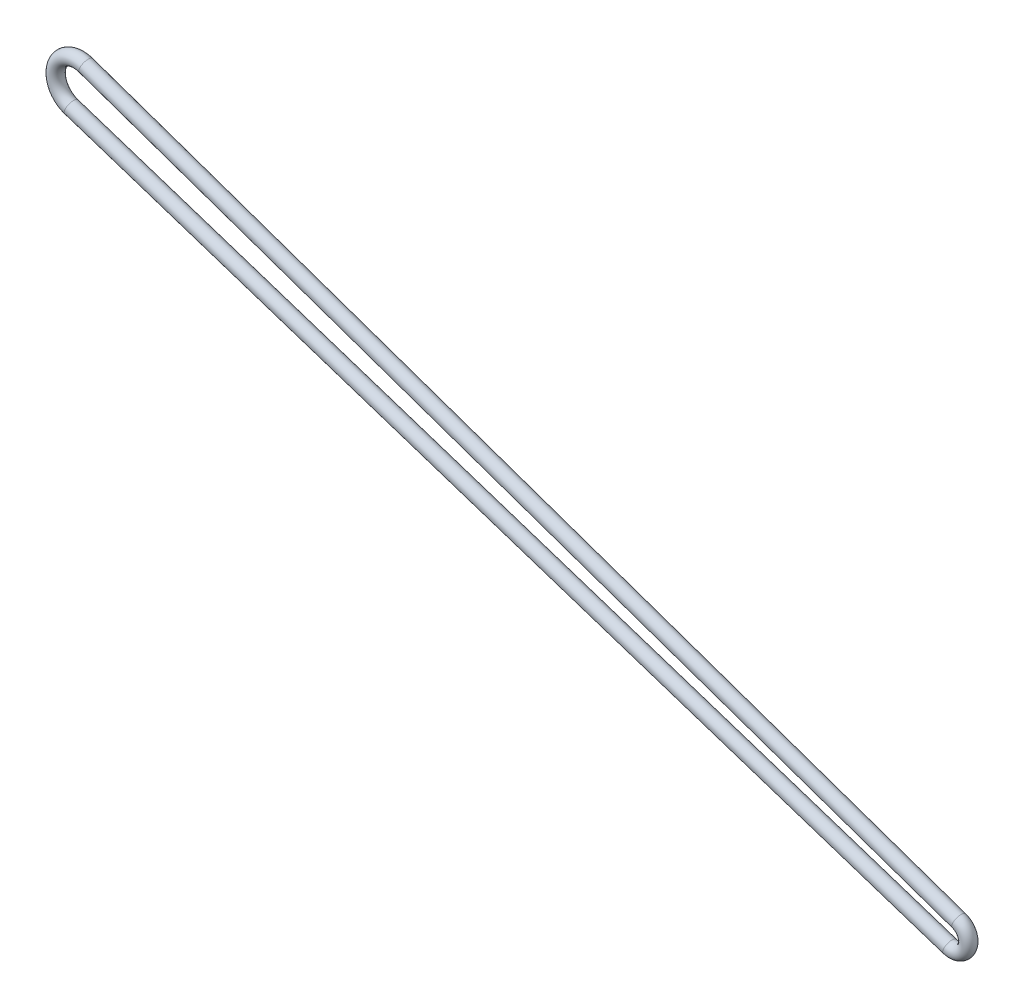
SolidWorks part; units mm, degrees
ref_plane "前视基准面" through (0, 0, 0) normal (0, 0, 1) x (1, 0, 0)
ref_plane "上视基准面" through (0, 0, 0) normal (0, 1, 0) x (1, 0, 0)
ref_plane "右视基准面" through (0, 0, 0) normal (1, 0, 0) x (0, 0, -1)
sketch "草图2" plane through (0, 0, 0) normal (0, 0, 1) x (1, 0, 0)
  line L0 (0, 0) -> (1, 0) construction
  line L1 (0, 0) -> (0, 1) construction
  line L2 (317.0425, 88.4994) -> (124.3039, 151.6372)
  line L3 (127.5057, 161.1103) -> (319.0276, 94.3728)
  arc A0 (319.0276, 94.3728) -> (317.0425, 88.4994) centre (318.0075, 91.4454) cw
  arc A1 (124.3039, 151.6372) -> (127.5057, 161.1103) centre (125.8604, 156.3887) cw
sweep "扫描19" add path "草图2" circular profile diameter 3 parameters "D3"=3
